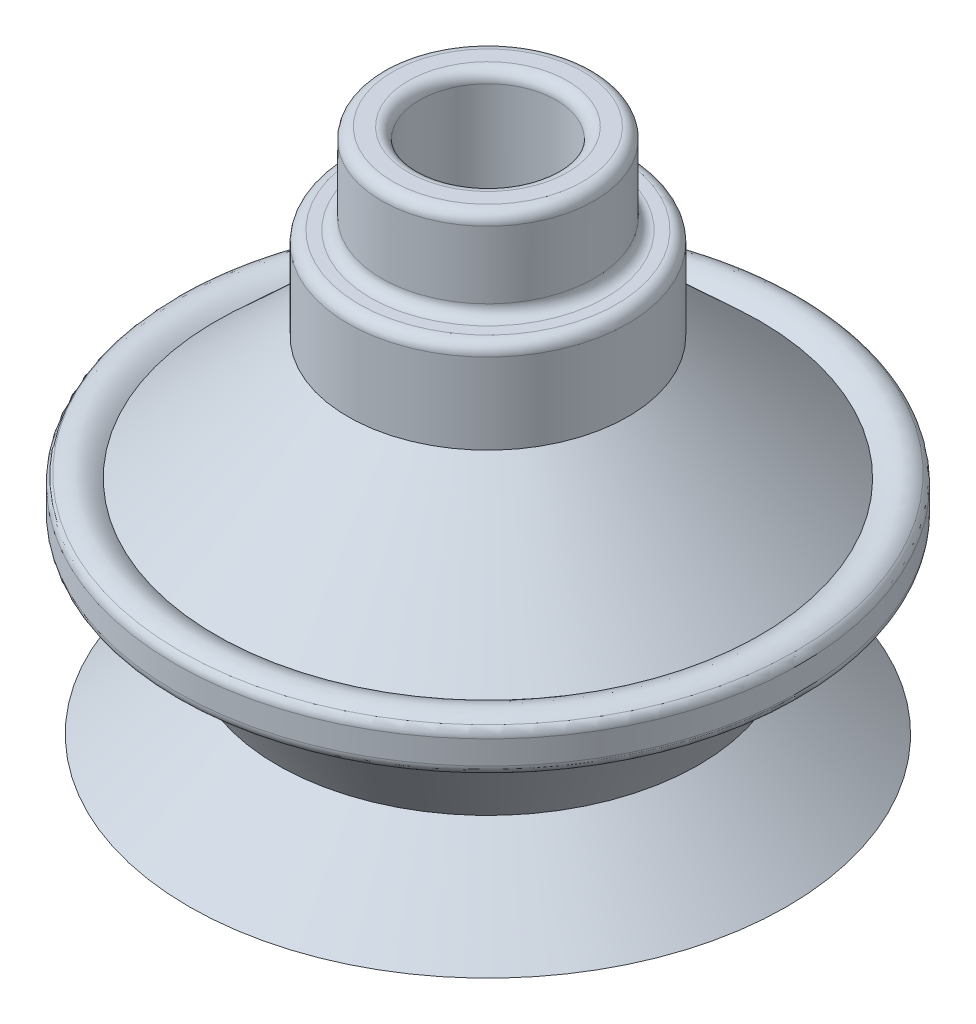
SolidWorks part; units mm, degrees
ref_plane "Front Plane" through (0, 0, 0) normal (0, 0, 1) x (1, 0, 0)
ref_plane "Top Plane" through (0, 0, 0) normal (0, 1, 0) x (1, 0, 0)
ref_plane "Right Plane" through (0, 0, 0) normal (1, 0, 0) x (0, 0, -1)
sketch "Sketch1" plane through (0, 0, 0) normal (0, 1, 0) x (1, 0, 0)
  circle A0 centre (0, 0) radius 4.75
  circle A1 centre (0, 0) radius 3.05
  dimension "D1" = 9.5
  dimension "D2" = 6.1
extrude "Boss-Extrude1" add sketch "Sketch1" along normal blind 4
sketch "Sketch2" plane through (0, 0, 0) normal (0, -1, 0) x (1, 0, 0)
  circle A0 centre (0, 0) radius 6.25
  circle A3 centre (0, 0) radius 3.05 construction
  circle A4 centre (0, 0) radius 3.05
  dimension "D1" = 12.5
extrude "Boss-Extrude2" add sketch "Sketch2" along normal blind 4.1
ref_plane "Plane1" through (0, -9.6, 0) normal (0, -1, 0) x (-1, 0, 0)
sketch "Sketch3" plane through (0, -9.6, 0) normal (0, -1, 0) x (-1, 0, 0)
  circle A0 centre (0, 0) radius 12.15
  circle A1 centre (0, 0) radius 11.15
  dimension "D1" = 24.3
  dimension "D2" = 22.3
sketch "Sketch4" plane through (0, -4.1, 0) normal (0, -1, 0) x (1, 0, 0)
  circle A0 centre (0, 0) radius 3.05 construction
  circle A1 centre (0, 0) radius 6.25
  circle A2 centre (0, 0) radius 6.25
  circle A3 centre (0, 0) radius 3.05
  dimension "D1" = 0
sketch "Sketch5" plane through (0, 0, 0) normal (0, 0, 1) x (1, 0, 0)
  line L0 (3.05, -4.1) -> (11.15, -9.6)
  line L1 (-11.15, -9.6) -> (11.15, -9.6) construction
  line L2 (6.25, -4.1) -> (12.15, -9.6)
  line L3 (-12.15, -9.6) -> (12.15, -9.6) construction
  line L4 (3.05, -4.1) -> (6.25, -4.1)
  line L5 (11.15, -9.6) -> (12.15, -9.6)
  line L6 (0, -9.6) -> (0, -6.6922) construction
revolve "Revolve1" add sketch "Sketch5" angle 360 about L6
sketch "Sketch6" plane through (0, 0, 0) normal (0, 0, 1) x (1, 0, 0)
  line L0 (11.15, -9.6) -> (11.15, -11.1)
  line L1 (-12.15, -9.6) -> (12.15, -9.6) construction
  line L2 (0, -9.6) -> (0, -8.3969) construction
  line L3 (13.95, -9.6) -> (13.95, -11.1)
  line L4 (-55, -9.6) -> (55, -9.6) construction
  line L5 (11.15, -11.1) -> (12.2428, -11.1)
  line L6 (12.15, -9.6) -> (11.15, -9.6)
  line L7 (12.15, -9.6) -> (6.25, -4.1) construction
  spline S0 degree 2 poles (13.95, -11.1) (13.214, -11.861) (12.2428, -11.1) knots 0 0 0 1 1 1
  spline S1 degree 2 poles (12.15, -9.6) (13.1821, -8.8059) (13.95, -9.6) knots 0 0 0 1 1 1
  dimension "D1" = 11.15
  dimension "D2" = 1.5
  dimension "D3" = 1.5
  dimension "D4" = 27.9
revolve "Revolve2" add sketch "Sketch6" angle 360 about L2
ref_plane "Plane2" through (0, -16, 0) normal (0, 1, 0) x (1, 0, 0)
sketch "Sketch7" plane through (0, -16, 0) normal (0, 1, 0) x (1, 0, 0)
  circle A0 centre (0, 0) radius 9.4
  circle A1 centre (0, 0) radius 8.5
  dimension "D1" = 18.8
  dimension "D2" = 17
sketch "Sketch8" plane through (0, 0, 0) normal (0, 0, 1) x (1, 0, 0)
  line L0 (11.15, -11.4805) -> (9.1, -16)
  line L1 (-13.1552, -11.4805) -> (13.1552, -11.4805) construction
  line L2 (9.4, -16) -> (-9.4, -16) construction
  line L3 (0, -11.4805) -> (0, -10.4025) construction
  line L4 (12.2428, -11.4805) -> (9.4, -16)
  line L5 (11.15, -11.4805) -> (12.2428, -11.4805)
  line L6 (9.1, -16) -> (9.4, -16)
  dimension "D1" = 22.3
  dimension "D2" = 18.2
  dimension "D3" = 24.4855
revolve "Revolve3" add sketch "Sketch8" angle 360 about L3
ref_plane "Plane3" through (0, -19.5, 0) normal (0, 1, 0) x (1, 0, 0)
sketch "Sketch9" plane through (0, 0, 0) normal (0, 0, 1) x (1, 0, 0)
  line L0 (0, -16) -> (0, -18.2861) construction
  line L2 (3.7358, -19.5) -> (8.3091, -19.5) construction
  line L4 (9.4, -16) -> (13.35, -19.5)
  line L5 (12.75, -19.5) -> (9.1, -16)
  line L6 (9.4, -16) -> (-9.4, -16) construction
  line L7 (9.1, -16) -> (9.4, -16)
  line L8 (12.75, -19.5) -> (13.35, -19.5)
  dimension "D1" = 26.7
  dimension "D2" = 0.6
revolve "Revolve4" add sketch "Sketch9" angle 360 about L0
fillet "Fillet1" radius 0.5 4 edges at (0, 0, -6.25) (0, 0, 4.75) (0, 4, 3.05) (0, 4, 4.75)
fillet "Fillet2" radius 0.5 2 edges at (0, -9.6, -13.95) (0, -11.1, -13.95)
